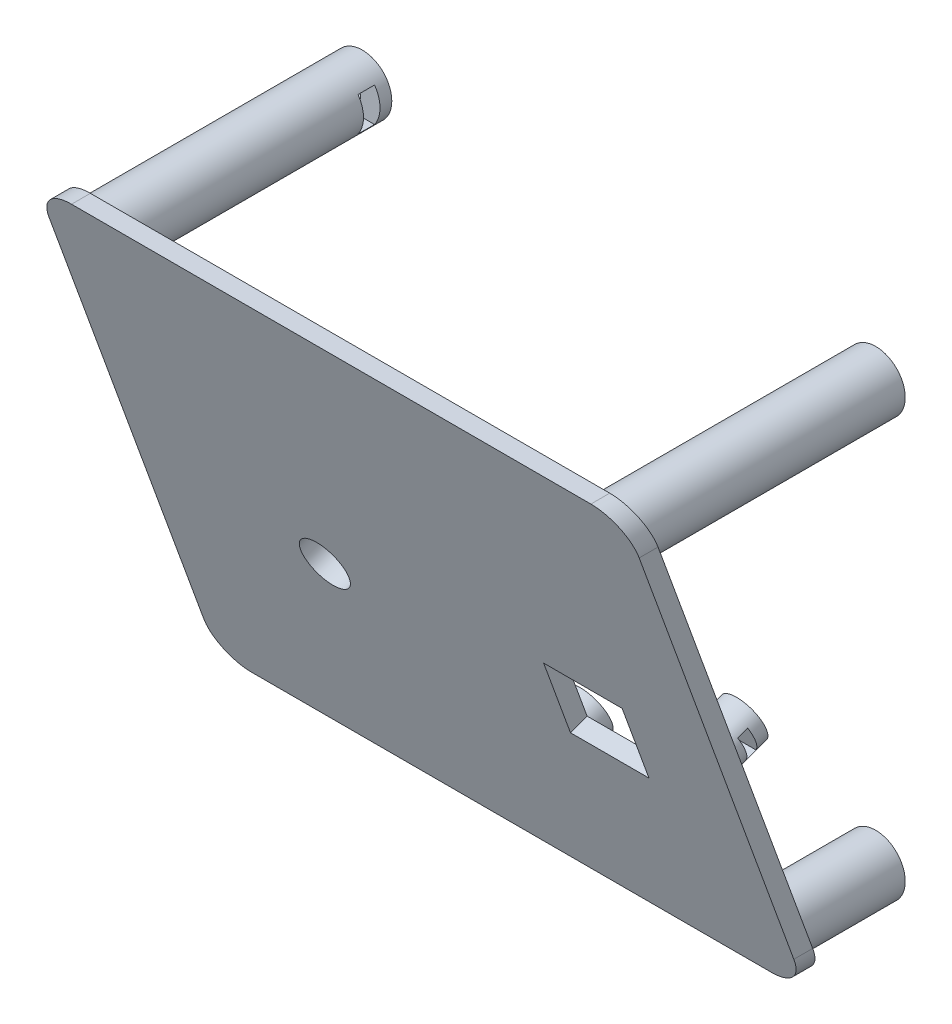
SolidWorks part; units mm, degrees
ref_plane "前视基准面" through (0, 0, 0) normal (0, 0, 1) x (1, 0, 0)
ref_plane "上视基准面" through (0, 0, 0) normal (0, 1, 0) x (1, 0, 0)
ref_plane "右视基准面" through (0, 0, 0) normal (1, 0, 0) x (0, 0, -1)
other "Configuration Table"
sketch "草图1" plane through (0, 0, 0) normal (0, 0, 1) x (1, 0, 0)
  line L0 (6, 0) -> (94, 0)
  line L1 (100, 6) -> (100, 78)
  line L2 (94, 84) -> (6, 84)
  line L3 (0, 78) -> (0, 6)
  arc A0 (94, 0) -> (100, 6) centre (94, 6) ccw
  arc A1 (100, 78) -> (94, 84) centre (94, 78) ccw
  arc A2 (6, 84) -> (0, 78) centre (6, 78) ccw
  arc A3 (0, 6) -> (6, 0) centre (6, 6) ccw
extrude "Lid_blank" add sketch "草图1" along normal blind 56
sketch "草图2" plane through (0, 0, 0) normal (1, 0, 0) x (0, 0, -1)
  line L0 (-13.9131, -20) -> (-61.2293, 110)
  line L1 (-61.2293, 110) -> (-120, 110)
  line L2 (-120, 110) -> (-120, -20)
  line L3 (-120, -20) -> (-13.9131, -20)
extrude "Outer_panel_20deg" cut sketch "草图2" against normal through all and the other way through all
sketch "草图3" plane through (0, 0, 0) normal (1, 0, 0) x (0, 0, -1)
  line L0 (-10.7206, -20) -> (-58.0367, 110)
  line L1 (-58.0367, 110) -> (30, 110)
  line L2 (30, 110) -> (30, -20)
  line L3 (30, -20) -> (-10.7206, -20)
extrude "Panel_3mm" cut sketch "草图3" against normal through all and the other way through all
sketch "草图4" plane through (0, 0, 0) normal (0, 0, 1) x (1, 0, 0)
  circle A0 centre (6.5, 6.5) radius 5
extrude "Hidden_case_post_0" add sketch "草图4" along normal blind 22.8782 from offset 3
sketch "草图5" plane through (0, 0, 0) normal (0, 0, 1) x (1, 0, 0)
  circle A0 centre (93.5, 6.5) radius 5
extrude "Hidden_case_post_1" add sketch "草图5" along normal blind 22.8782 from offset 3
sketch "草图6" plane through (0, 0, 0) normal (0, 0, 1) x (1, 0, 0)
  circle A0 centre (6.5, 77.5) radius 5
extrude "Hidden_case_post_2" add sketch "草图6" along normal blind 48.7201 from offset 3
sketch "草图7" plane through (0, 0, 0) normal (0, 0, 1) x (1, 0, 0)
  circle A0 centre (93.5, 77.5) radius 5
extrude "Hidden_case_post_3" add sketch "草图7" along normal blind 48.7201 from offset 3
sketch "草图8" plane through (0, 0, 0) normal (1, 0, 0) x (0, 0, -1)
  line L0 (-13.9131, -20) -> (-61.2293, 110)
  line L1 (-61.2293, 110) -> (-120, 110)
  line L2 (-120, 110) -> (-120, -20)
  line L3 (-120, -20) -> (-13.9131, -20)
extrude "Flush_outer_surface" cut sketch "草图8" against normal through all and the other way through all
sketch "草图9" plane through (0, 0, 0) normal (0, 0, 1) x (1, 0, 0)
  circle A0 centre (6.5, 6.5) radius 1.7
extrude "Blind_M3_0" cut sketch "草图9" along normal blind 9.5 from offset 3
sketch "草图10" plane through (0, 0, 0) normal (1, 0, 0) x (0, 0, -1)
  line L0 (-5, 3.6) -> (-5, 9.4)
  line L1 (-5, 9.4) -> (-7.8, 9.4)
  line L2 (-7.8, 9.4) -> (-7.8, 3.6)
  line L3 (-7.8, 3.6) -> (-5, 3.6)
extrude "M3_side_load_nut_0" [suppressed] cut sketch "草图10" along normal blind 9.4 from offset 3.1
sketch "草图11" plane through (0, 0, 0) normal (0, 0, 1) x (1, 0, 0)
  circle A0 centre (93.5, 6.5) radius 1.7
extrude "Blind_M3_1" cut sketch "草图11" along normal blind 9.5 from offset 3
sketch "草图12" plane through (0, 0, 0) normal (1, 0, 0) x (0, 0, -1)
  line L0 (-5, 3.6) -> (-5, 9.4)
  line L1 (-5, 9.4) -> (-7.8, 9.4)
  line L2 (-7.8, 9.4) -> (-7.8, 3.6)
  line L3 (-7.8, 3.6) -> (-5, 3.6)
extrude "M3_side_load_nut_1" [suppressed] cut sketch "草图12" along normal blind 9.4 from offset 87.5
sketch "草图13" plane through (0, 0, 0) normal (0, 0, 1) x (1, 0, 0)
  circle A0 centre (6.5, 77.5) radius 1.7
extrude "Blind_M3_2" cut sketch "草图13" along normal blind 9.5 from offset 3
sketch "草图14" plane through (0, 0, 0) normal (1, 0, 0) x (0, 0, -1)
  line L0 (-5, 74.6) -> (-5, 80.4)
  line L1 (-5, 80.4) -> (-7.8, 80.4)
  line L2 (-7.8, 80.4) -> (-7.8, 74.6)
  line L3 (-7.8, 74.6) -> (-5, 74.6)
extrude "M3_side_load_nut_2" [suppressed] cut sketch "草图14" along normal blind 9.4 from offset 3.1
sketch "草图15" plane through (0, 0, 0) normal (0, 0, 1) x (1, 0, 0)
  circle A0 centre (93.5, 77.5) radius 1.7
extrude "Blind_M3_3" cut sketch "草图15" along normal blind 9.5 from offset 3
sketch "草图16" plane through (0, 0, 0) normal (1, 0, 0) x (0, 0, -1)
  line L0 (-5, 74.6) -> (-5, 80.4)
  line L1 (-5, 80.4) -> (-7.8, 80.4)
  line L2 (-7.8, 80.4) -> (-7.8, 74.6)
  line L3 (-7.8, 74.6) -> (-5, 74.6)
extrude "M3_side_load_nut_3" [suppressed] cut sketch "草图16" along normal blind 9.4 from offset 87.5
sketch "草图17" plane through (0, -6.8111, 18.7135) normal (0, -0.342, 0.9397) x (1, 0, 0)
  circle A0 centre (31, 44.2483) radius 4.1
extrude "Shaft_D8p2" cut sketch "草图17" against normal blind 5
sketch "草图18" plane through (0, -6.8111, 18.7135) normal (0, -0.342, 0.9397) x (1, 0, 0)
  line L0 (70.35, 37.5983) -> (83.65, 37.5983)
  line L1 (83.65, 37.5983) -> (83.65, 50.8983)
  line L2 (83.65, 50.8983) -> (70.35, 50.8983)
  line L3 (70.35, 50.8983) -> (70.35, 37.5983)
extrude "Button_13p3_clearance" cut sketch "草图18" against normal blind 5
sketch "草图19" plane through (0, -5.7851, 15.8944) normal (0, 0.342, -0.9397) x (-1, 0, 0)
  circle A0 centre (-44.5, 36.2483) radius 4
extrude "Encoder_right_blind_post" add sketch "草图19" along normal blind 11.07
sketch "草图20" plane through (0, -6.8111, 18.7135) normal (0, -0.342, 0.9397) x (1, 0, 0)
  circle A0 centre (44.5, 36.2483) radius 1.15
extrude "Encoder_right_blind_screw" cut sketch "草图20" along normal blind 5 from offset 14.07 offset against normal yes
sketch "草图21" plane through (0, 0, 0) normal (1, 0, 0) x (0, 0, -1)
  line L0 (-19.0508, 29.4059) -> (-20.4873, 33.3526)
  line L1 (-20.4873, 33.3526) -> (-22.1787, 32.737)
  line L2 (-22.1787, 32.737) -> (-20.7422, 28.7903)
  line L3 (-20.7422, 28.7903) -> (-19.0508, 29.4059)
extrude "Encoder_right_M2_side_nut" [suppressed] cut sketch "草图21" along normal blind 7.5 from offset 42
sketch "草图22" plane through (0, -5.7851, 15.8944) normal (0, 0.342, -0.9397) x (-1, 0, 0)
  circle A0 centre (-17.5, 60.2483) radius 4
extrude "Encoder_left_blind_post" add sketch "草图22" along normal blind 11.07
sketch "草图23" plane through (0, -6.8111, 18.7135) normal (0, -0.342, 0.9397) x (1, 0, 0)
  circle A0 centre (17.5, 60.2483) radius 1.15
extrude "Encoder_left_blind_screw" cut sketch "草图23" along normal blind 5 from offset 14.07 offset against normal yes
sketch "草图24" plane through (0, 0, 0) normal (1, 0, 0) x (0, 0, -1)
  line L0 (-27.2593, 51.9585) -> (-28.6958, 55.9052)
  line L1 (-28.6958, 55.9052) -> (-30.3872, 55.2896)
  line L2 (-30.3872, 55.2896) -> (-28.9507, 51.3429)
  line L3 (-28.9507, 51.3429) -> (-27.2593, 51.9585)
extrude "Encoder_left_M2_side_nut" [suppressed] cut sketch "草图24" along normal blind 7.5 from offset 15
sketch "草图25" plane through (0, -5.7851, 15.8944) normal (0, 0.342, -0.9397) x (-1, 0, 0)
  circle A0 centre (-60, 25.2483) radius 4
extrude "Button_left_blind_post" add sketch "草图25" along normal blind 6.7
sketch "草图26" plane through (0, -6.8111, 18.7135) normal (0, -0.342, 0.9397) x (1, 0, 0)
  circle A0 centre (60, 25.2483) radius 1.15
extrude "Button_left_blind_screw" cut sketch "草图26" along normal blind 5 from offset 9.7 offset against normal yes
sketch "草图27" plane through (0, 0, 0) normal (1, 0, 0) x (0, 0, -1)
  line L0 (-19.395, 17.5747) -> (-20.8315, 21.5214)
  line L1 (-20.8315, 21.5214) -> (-22.523, 20.9057)
  line L2 (-22.523, 20.9057) -> (-21.0865, 16.959)
  line L3 (-21.0865, 16.959) -> (-19.395, 17.5747)
extrude "Button_left_M2_side_nut" [suppressed] cut sketch "草图27" along normal blind 7.5 from offset 57.5
sketch "草图28" plane through (0, -5.7851, 15.8944) normal (0, 0.342, -0.9397) x (-1, 0, 0)
  circle A0 centre (-93.3, 45.2483) radius 3.8
extrude "Button_right_blind_post" add sketch "草图28" along normal blind 6.7
sketch "草图29" plane through (0, -6.8111, 18.7135) normal (0, -0.342, 0.9397) x (1, 0, 0)
  circle A0 centre (93.3, 45.2483) radius 1.15
extrude "Button_right_blind_screw" cut sketch "草图29" along normal blind 5 from offset 9.7 offset against normal yes
sketch "草图30" plane through (0, 0, 0) normal (1, 0, 0) x (0, 0, -1)
  line L0 (-26.2354, 36.3685) -> (-27.6719, 40.3152)
  line L1 (-27.6719, 40.3152) -> (-29.3634, 39.6996)
  line L2 (-29.3634, 39.6996) -> (-27.9269, 35.7529)
  line L3 (-27.9269, 35.7529) -> (-26.2354, 36.3685)
extrude "Button_right_M2_side_nut" [suppressed] cut sketch "草图30" along normal blind 7.5 from offset 90.8
sketch "M3_hex_side_nut_0_Sketch" plane through (0, 0, 0) normal (0, 0, 1) x (1, 0, 0)
  line L0 (3.1514, 6.5) -> (4.8257, 3.6)
  line L1 (4.8257, 3.6) -> (14.5, 3.6)
  line L2 (14.5, 3.6) -> (14.5, 9.4)
  line L3 (14.5, 9.4) -> (4.8257, 9.4)
  line L4 (4.8257, 9.4) -> (3.1514, 6.5)
extrude "M3_hex_side_nut_0" cut sketch "M3_hex_side_nut_0_Sketch" along normal blind 2.8 from offset 5
sketch "M3_hex_side_nut_1_Sketch" plane through (0, 0, 0) normal (0, 0, 1) x (1, 0, 0)
  line L0 (96.8486, 6.5) -> (95.1743, 3.6)
  line L1 (95.1743, 3.6) -> (85.5, 3.6)
  line L2 (85.5, 3.6) -> (85.5, 9.4)
  line L3 (85.5, 9.4) -> (95.1743, 9.4)
  line L4 (95.1743, 9.4) -> (96.8486, 6.5)
extrude "M3_hex_side_nut_1" cut sketch "M3_hex_side_nut_1_Sketch" along normal blind 2.8 from offset 5
sketch "M3_hex_side_nut_2_Sketch" plane through (0, 0, 0) normal (0, 0, 1) x (1, 0, 0)
  line L0 (3.1514, 77.5) -> (4.8257, 74.6)
  line L1 (4.8257, 74.6) -> (14.5, 74.6)
  line L2 (14.5, 74.6) -> (14.5, 80.4)
  line L3 (14.5, 80.4) -> (4.8257, 80.4)
  line L4 (4.8257, 80.4) -> (3.1514, 77.5)
extrude "M3_hex_side_nut_2" cut sketch "M3_hex_side_nut_2_Sketch" along normal blind 2.8 from offset 5
sketch "M3_hex_side_nut_3_Sketch" plane through (0, 0, 0) normal (0, 0, 1) x (1, 0, 0)
  line L0 (96.8486, 77.5) -> (95.1743, 74.6)
  line L1 (95.1743, 74.6) -> (85.5, 74.6)
  line L2 (85.5, 74.6) -> (85.5, 80.4)
  line L3 (85.5, 80.4) -> (95.1743, 80.4)
  line L4 (95.1743, 80.4) -> (96.8486, 77.5)
extrude "M3_hex_side_nut_3" cut sketch "M3_hex_side_nut_3_Sketch" along normal blind 2.8 from offset 5
sketch "Encoder_right_hex_M2_nut_Sketch" plane through (0, -6.8111, 18.7135) normal (0, -0.342, 0.9397) x (1, 0, 0)
  line L0 (42.0751, 36.2483) -> (43.2876, 34.1483)
  line L1 (43.2876, 34.1483) -> (52.5, 34.1483)
  line L2 (52.5, 34.1483) -> (52.5, 38.3483)
  line L3 (52.5, 38.3483) -> (43.2876, 38.3483)
  line L4 (43.2876, 38.3483) -> (42.0751, 36.2483)
extrude "Encoder_right_hex_M2_nut" cut sketch "Encoder_right_hex_M2_nut_Sketch" against normal blind 1.8 from offset 10.27 offset against normal yes
sketch "Encoder_left_hex_M2_nut_Sketch" plane through (0, -6.8111, 18.7135) normal (0, -0.342, 0.9397) x (1, 0, 0)
  line L0 (15.0751, 60.2483) -> (16.2876, 58.1483)
  line L1 (16.2876, 58.1483) -> (25.5, 58.1483)
  line L2 (25.5, 58.1483) -> (25.5, 62.3483)
  line L3 (25.5, 62.3483) -> (16.2876, 62.3483)
  line L4 (16.2876, 62.3483) -> (15.0751, 60.2483)
extrude "Encoder_left_hex_M2_nut" cut sketch "Encoder_left_hex_M2_nut_Sketch" against normal blind 1.8 from offset 10.27 offset against normal yes
sketch "Button_left_hex_M2_nut_Sketch" plane through (0, -6.8111, 18.7135) normal (0, -0.342, 0.9397) x (1, 0, 0)
  line L0 (57.5751, 25.2483) -> (58.7876, 23.1483)
  line L1 (58.7876, 23.1483) -> (68, 23.1483)
  line L2 (68, 23.1483) -> (68, 27.3483)
  line L3 (68, 27.3483) -> (58.7876, 27.3483)
  line L4 (58.7876, 27.3483) -> (57.5751, 25.2483)
extrude "Button_left_hex_M2_nut" cut sketch "Button_left_hex_M2_nut_Sketch" against normal blind 1.8 from offset 5.9 offset against normal yes
sketch "Button_right_hex_M2_nut_Sketch" plane through (0, -6.8111, 18.7135) normal (0, -0.342, 0.9397) x (1, 0, 0)
  line L0 (90.8751, 45.2483) -> (92.0876, 43.1483)
  line L1 (92.0876, 43.1483) -> (101.3, 43.1483)
  line L2 (101.3, 43.1483) -> (101.3, 47.3483)
  line L3 (101.3, 47.3483) -> (92.0876, 47.3483)
  line L4 (92.0876, 47.3483) -> (90.8751, 45.2483)
extrude "Button_right_hex_M2_nut" cut sketch "Button_right_hex_M2_nut_Sketch" against normal blind 1.8 from offset 5.9 offset against normal yes
